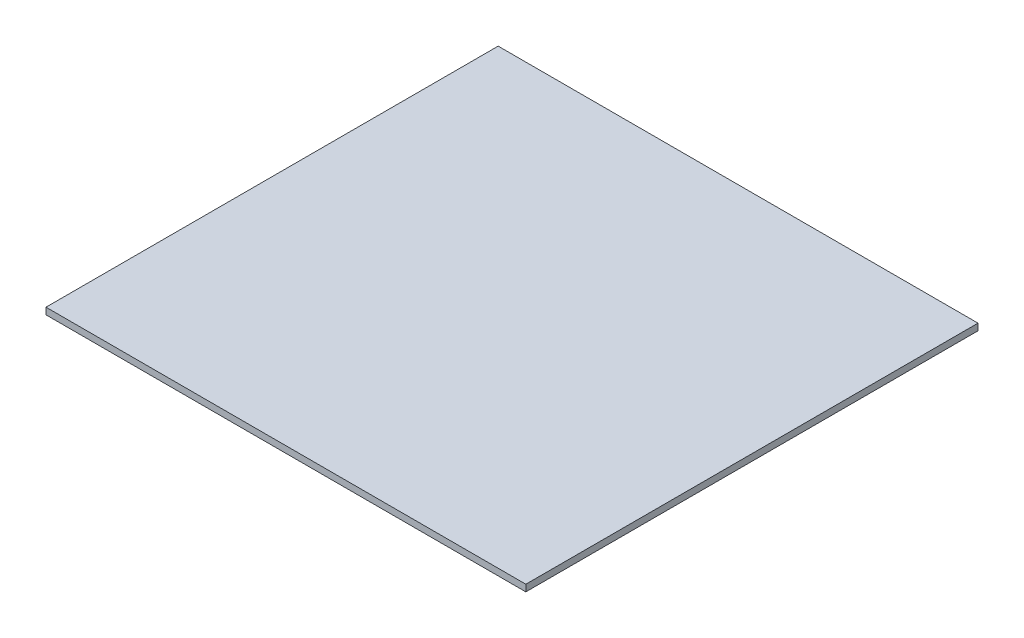
SolidWorks part; units mm, degrees
material "Polyethylene Cross-Linked"
ref_plane "Front Plane" through (0, 0, 0) normal (0, 0, 1) x (1, 0, 0)
ref_plane "Top Plane" through (0, 0, 0) normal (0, 1, 0) x (1, 0, 0)
ref_plane "Right Plane" through (0, 0, 0) normal (1, 0, 0) x (0, 0, -1)
sketch "Sketch1" plane through (0, 0, 0) normal (0, 1, 0) x (1, 0, 0)
  line L1 (0, 0) -> (229.108, 0)
  line L3 (0, 215.9) -> (229.108, 215.9)
  line L8 (229.108, 215.9) -> (229.108, 0)
  line L41 (0, 0) -> (0, 215.9)
extrude "Boss-Extrude1" add sketch "Sketch1" along normal blind 3.175
ref_plane "Plane1" through (229.108, 3.175, -215.9) normal (-1, 0, 0) x (0, 0, 1)
sketch "Sketch2" plane through (229.108, 3.175, -215.9) normal (-1, 0, 0) x (0, 0, 1)
